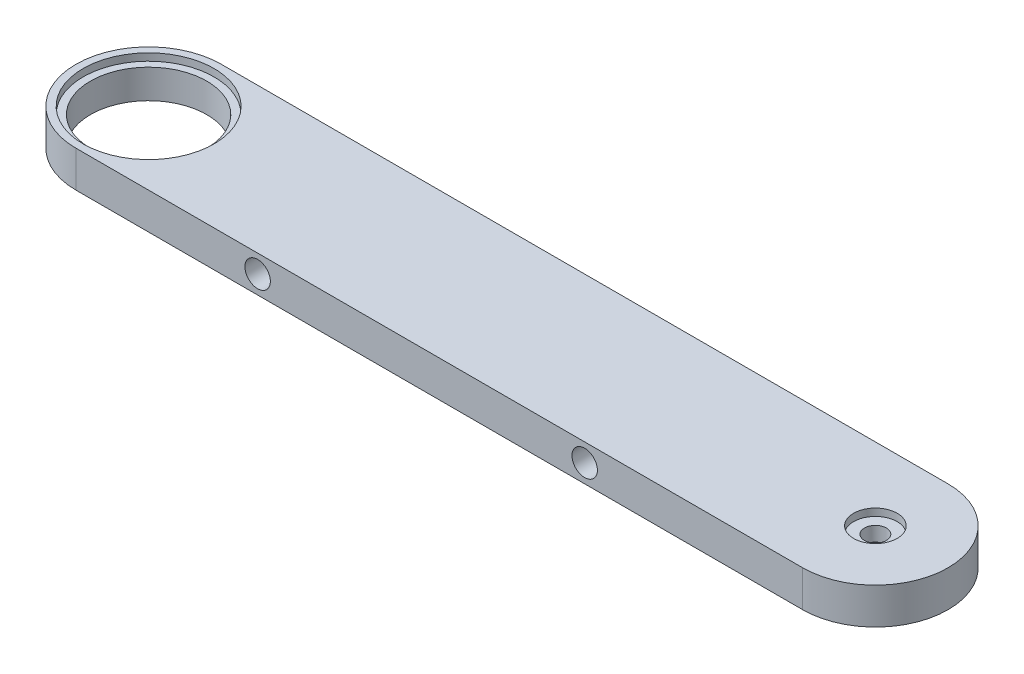
SolidWorks part; units mm, degrees
ref_plane "Front Plane" through (0, 0, 0) normal (0, 0, 1) x (1, 0, 0)
ref_plane "Top Plane" through (0, 0, 0) normal (0, 1, 0) x (1, 0, 0)
ref_plane "Right Plane" through (0, 0, 0) normal (1, 0, 0) x (0, 0, -1)
sketch "Sketch1" plane through (0, 0, 0) normal (0, 1, 0) x (1, 0, 0)
  line L0 (-50, 10) -> (-60, 10)
  line L1 (-50, 10) -> (50, 10)
  line L3 (-60, -10) -> (50, -10)
  arc A1 (50, -10) -> (50, 10) centre (50, 0) ccw
  arc A3 (-60, 10) -> (-60, -10) centre (-60, 0) ccw
  point P0 (0, 0)
  dimension "D1" = 110
  dimension "D2" = 20
extrude "Boss-Extrude1" add sketch "Sketch1" along normal blind 5
sketch "Sketch2" plane through (0, 0, 0) normal (0, -1, 0) x (1, 0, 0)
  line L0 (50, -10) -> (50, 10)
  circle A0 centre (50, 0) radius 4
  dimension "D1" = 8
extrude "Cut-Extrude1" cut sketch "Sketch2" against normal blind 2 contours L0 A0 | L0 A0 region at (48.3023, 0, 0) region at (51.6977, 0, 0)
sketch "Sketch3" plane through (0, 5, 0) normal (0, 1, 0) x (1, 0, 0)
  line L0 (50, 10) -> (50, -10)
  circle A0 centre (50, 0) radius 3
  dimension "D1" = 6
extrude "Cut-Extrude2" cut sketch "Sketch3" against normal blind 1 contours L0 A0 | L0 A0 region at (51.2732, 5, 0) region at (48.7268, 5, 0)
sketch "Sketch6" plane through (0, 4, 0) normal (0, 1, 0) x (1, 0, 0)
  circle A0 centre (50, 0) radius 1.5
  dimension "D1" = 3
extrude "Cut-Extrude5" cut sketch "Sketch6" against normal through all
sketch "Sketch7" plane through (0, 5, 0) normal (0, 1, 0) x (1, 0, 0)
  circle A0 centre (-50, 0) radius 8
  point P0 (-50, 0)
  point P1 (50, 0)
  dimension "D2" = 16
  dimension "D1" = 100
extrude "Cut-Extrude6" cut sketch "Sketch7" against normal through all
sketch "Sketch8" plane through (0, 5, 0) normal (0, 1, 0) x (1, 0, 0)
  circle A0 centre (-50, 0) radius 9
  dimension "D1" = 18
extrude "Cut-Extrude7" cut sketch "Sketch8" against normal blind 1
sketch "Sketch9" plane through (0, 5, 0) normal (0, 1, 0) x (1, 0, 0)
  line L0 (-50, -10) -> (-60, -10)
  line L2 (-60, 10) -> (-50, 10)
  arc A0 (-50, 10) -> (-50, -10) centre (-50, 0) ccw
  arc A1 (-60, 10) -> (-60, -10) centre (-60, 0) ccw
extrude "Cut-Extrude8" cut sketch "Sketch9" against normal through all
sketch "Sketch10" plane through (0, 0, 10) normal (0, 0, 1) x (1, 0, 0)
  line L0 (-50, 0) -> (-50, 5) construction
  line L2 (-50, 5) -> (50, 5) construction
  circle A0 centre (-25, 2.5) radius 1.75
  circle A1 centre (20, 2.5) radius 1.75
  point P0 (-25, 2.5)
  point P5 (20, 2.5)
  dimension "D4" = 3.5
  dimension "D5" = 3.5
  dimension "D1" = 25
  dimension "D2" = 2.5
  dimension "D3" = 70
extrude "Cut-Extrude9" cut sketch "Sketch10" against normal blind 8
